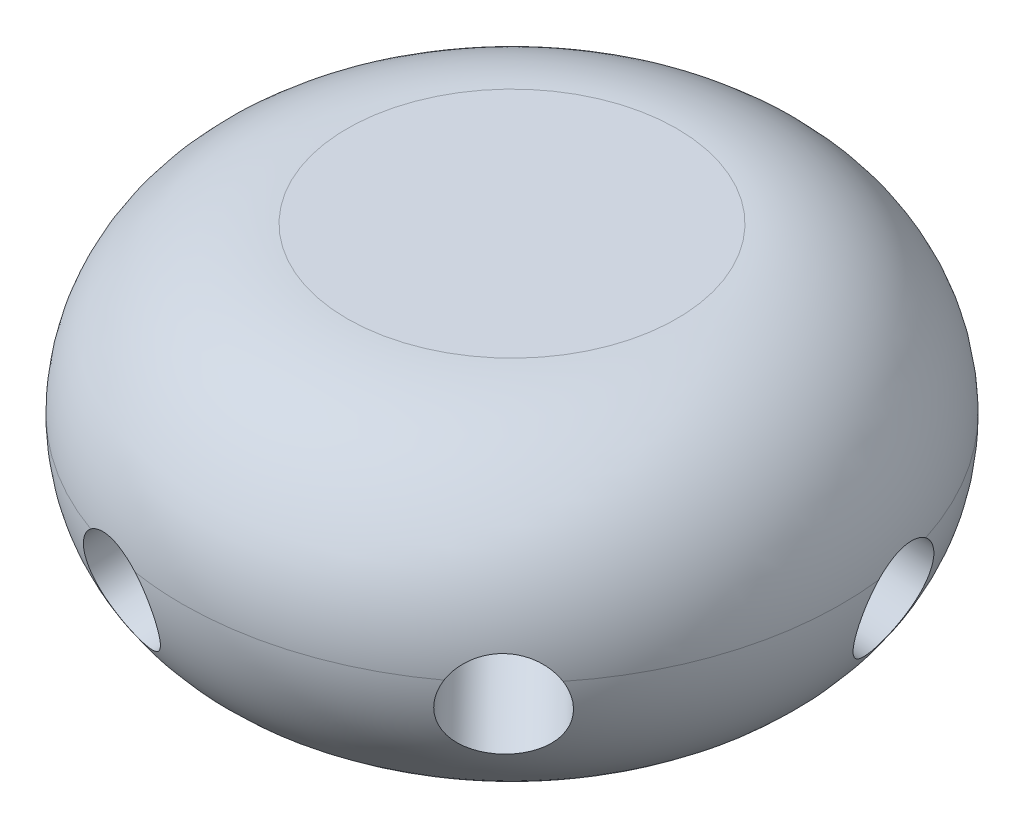
SolidWorks part; units mm, degrees
ref_plane "Front Plane" through (0, 0, 0) normal (0, 0, 1) x (1, 0, 0)
ref_plane "Top Plane" through (0, 0, 0) normal (0, 1, 0) x (1, 0, 0)
ref_plane "Right Plane" through (0, 0, 0) normal (1, 0, 0) x (0, 0, -1)
sketch "Sketch1" plane through (0, 0, 0) normal (0, 1, 0) x (1, 0, 0)
  circle A0 centre (0, 0) radius 10
  dimension "D1" = 20
extrude "base" add sketch "Sketch1" along normal blind 3 and the other way blind 7
ref_axis "6hubaxis" through (0, 5.5, 0) along (0, -1, 0)
ref_plane "Plane1" through (2.6705, -1.0931, 2.7701) normal (-0.6676, 0.2733, -0.6925) x (-0.6559, 0.2243, 0.7208)
sketch "Sketch2" plane through (2.6705, -1.0931, 2.7701) normal (-0.6676, 0.2733, -0.6925) x (-0.6559, 0.2243, 0.7208)
  circle A0 centre (0, 0) radius 1.5 construction
  circle A1 centre (0, 0) radius 1.5
extrude "hole1" cut sketch "Sketch2" against normal through all
pattern_circular "hole1mirror" count 2 over 360 about axis through (0, 5.5, 0) along (0, -1, 0) of "hole1"
ref_plane "Plane2" through (-0.9417, -1.2361, 3.6858) normal (0.2354, 0.309, -0.9215) x (-0.9719, 0.0738, -0.2235)
sketch "Sketch3" plane through (-0.9417, -1.2361, 3.6858) normal (0.2354, 0.309, -0.9215) x (-0.9719, 0.0738, -0.2235)
  circle A0 centre (0, 0) radius 1.5 construction
  circle A1 centre (0, 0) radius 1.5
extrude "hole2" cut sketch "Sketch3" against normal through all
pattern_circular "hole2mirror" count 2 over 360 about axis through (0, 5.5, 0) along (0, -1, 0) of "hole2"
ref_plane "Plane3" through (-3.7178, -1.2361, 0.8061) normal (0.9295, 0.309, -0.2015) x (-0.1912, -0.0636, -0.9795)
sketch "Sketch4" plane through (-3.7178, -1.2361, 0.8061) normal (0.9295, 0.309, -0.2015) x (-0.1912, -0.0636, -0.9795)
  circle A0 centre (0, 0) radius 1.5 construction
  circle A1 centre (0, 0) radius 1.5
extrude "hole3" cut sketch "Sketch4" against normal through all
pattern_circular "hole3mirror" count 2 over 360 about axis through (0, 5.5, 0) along (0, -1, 0) of "hole3"
fillet "Fillet1" radius 5 2 edges at (0, -7, 10) (0, 3, 10)
